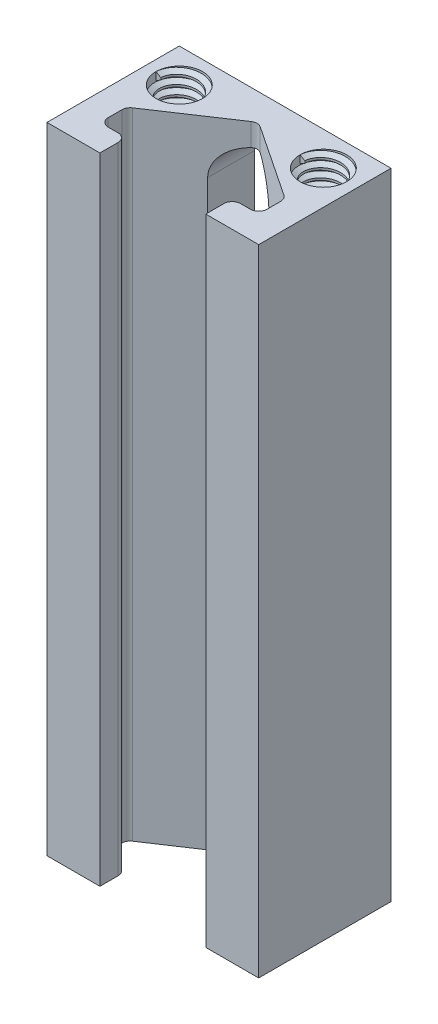
SolidWorks part; units mm, degrees
ref_plane "Front Plane" through (0, 0, 0) normal (0, 0, 1) x (1, 0, 0)
ref_plane "Top Plane" through (0, 0, 0) normal (0, 1, 0) x (1, 0, 0)
ref_plane "Right Plane" through (0, 0, 0) normal (1, 0, 0) x (0, 0, -1)
sketch "Sketch2" plane through (0, 0, 0) normal (0, 0, 1) x (1, 0, 0)
  line L0 (-71.4143, -70) -> (71.4143, -70)
  arc A0 (-71.4143, -70) -> (71.4143, -70) centre (0, 0) ccw
  point P5 (0, -70)
  point P6 (0, -100)
  dimension "D1" = 200
  dimension "D2" = 30
extrude "Boss-Extrude1" add sketch "Sketch2" along normal blind 127
sketch "Sketch3" plane through (0, 0, 0) normal (0, 1, 0) x (1, 0, 0)
  line L0 (-52.3643, -127) -> (-52.3643, -111.125)
  line L1 (71.4143, -127) -> (-71.4143, -127) construction
  line L2 (-52.3643, -111.125) -> (-26.9643, -111.125)
  line L3 (-26.9643, -111.125) -> (-26.9643, -127)
  line L4 (-26.9643, -127) -> (-33.3143, -127)
  line L5 (-33.3143, -127) -> (-33.3143, -123.825)
  line L6 (-33.3143, -123.825) -> (-30.1393, -123.825)
  line L7 (-30.1393, -123.825) -> (-30.1393, -120.65)
  line L8 (-30.1393, -120.65) -> (-39.6643, -114.3)
  line L9 (-39.6643, -114.3) -> (-49.1893, -120.65)
  line L10 (-49.1893, -120.65) -> (-49.1893, -123.825)
  line L11 (-49.1893, -123.825) -> (-46.0143, -123.825)
  line L12 (-46.0143, -123.825) -> (-46.0143, -127)
  line L13 (-46.0143, -127) -> (-52.3643, -127)
  line L14 (-71.4143, -127) -> (-71.4143, 0) construction
  point P1 (-52.3643, -111.125)
  point P5 (-26.9643, -111.125)
  point P6 (-27.4117, -111.125)
  point P16 (-51.891, -111.125)
  point P18 (-33.3143, -125.4125)
  dimension "D1" = 12.7
  dimension "D2" = 25.4
  dimension "D3" = 3.175
  dimension "D4" = 3.175
  dimension "D5" = 9.525
  dimension "D6" = 3.175
  dimension "D7" = 3.175
  dimension "D9" = 19.05
extrude "Boss-Extrude2" add sketch "Sketch3" along normal blind 76.2
fillet "Fillet1" radius 1 7 edges at (-46.0143, 38.1, 123.825) (-33.3143, 38.1, 123.825) (-30.1393, 38.1, 123.825) (-30.1393, 38.1, 120.65) (-39.6643, 38.1, 114.3) (-49.1893, 38.1, 120.65) (-49.1893, 38.1, 123.825)
sketch "Sketch5" plane through (0, 0, 111.125) normal (0, 0, -1) x (-1, 0, 0)
  line L0 (39.6643, 69.85) -> (39.6643, 6.35) construction
  line L1 (43.3393, 69.85) -> (43.3393, 6.35)
  line L2 (35.9893, 69.85) -> (35.9893, 6.35)
  line L3 (33.3143, 69.85) -> (46.0143, 69.85) construction
  line L6 (26.9643, 76.2) -> (52.3643, 76.2) construction
  line L7 (46.0143, 76.2) -> (46.0143, 0) construction
  line L8 (26.9643, 0) -> (52.3643, 0) construction
  line L9 (33.3143, 76.2) -> (33.3143, 0) construction
  arc A0 (43.3393, 69.85) -> (35.9893, 69.85) centre (39.6643, 69.85) ccw
  arc A1 (35.9893, 6.35) -> (43.3393, 6.35) centre (39.6643, 6.35) ccw
  point P2 (39.6643, 38.1)
  point P7 (46.0143, 31.75)
  point P12 (33.3143, 31.75)
  dimension "D1" = 7.35
  dimension "D2" = 6.35
  dimension "D3" = 6.35
extrude "Cut-Extrude1" cut sketch "Sketch5" against normal through all both and the other way through all
delete or keep bodies "Body-Delete/Keep 1" type delete bodies bodies 101
sketch "Sketch6" plane through (0, 76.2, 0) normal (0, 1, 0) x (1, 0, 0)
  line L0 (-48.3059, -115.1834) -> (-48.3059, -111.125) construction
  line L2 (-39.6643, -111.125) -> (-39.6643, -127) construction
  line L3 (-26.9643, -111.125) -> (-52.3643, -111.125) construction
  line L4 (-52.3643, -127) -> (-46.0143, -127) construction
  line L6 (-26.9643, -111.125) -> (-52.3643, -111.125) construction
  line L7 (-48.3059, -115.1834) -> (-52.3643, -115.1834) construction
  line L8 (-52.3643, -111.125) -> (-52.3643, -127) construction
  line L9 (-52.3643, -111.125) -> (-45.3793, -118.11) construction
  line L10 (-48.744, -120.3531) -> (-40.219, -114.6698) construction
  line L11 (-46.0546, -118.5602) -> (-46.7534, -117.5121) construction
  line L12 (-48.4587, -118.649) -> (-46.7534, -117.5121) construction
  line L13 (-51.1046, -115.1834) -> (-52.3643, -115.1834) construction
  circle A0 centre (-48.3059, -115.1834) radius 2.7987
  circle A3 centre (-31.0227, -115.1834) radius 2.7987
  dimension "D1" = 5.5974
extrude "Cut-Extrude2" cut sketch "Sketch6" against normal blind 25.4
thread "Thread1" pitch 1.0583 start angle 0, offset 0, length 0, pitch 1.0583, diameter 5.5974
ref_plane "Plane1" through (-51.1046, 76.2, 115.1834) normal (0, 0, 1) x (-1, 0, 0)
sketch "Thread Profile1" plane through (-51.1046, 76.2, 115.1834) normal (0, 0, 1) x (-1, 0, 0)
  line L0 (0, 0) -> (0, 1.0583) construction
  line L11 (0, 0) -> (0, 0.926)
  line L12 (0, 0.926) -> (-0.5728, 0.5953)
  line L13 (-0.5728, 0.5953) -> (-0.5728, 0.3307)
  line L15 (-0.5728, 0.3307) -> (0, 0)
  line L17 (-0.5728, 0.463) -> (0, 0.463) construction
  point P2 (0, 0)
  dimension "Pitch" = 1.0583
  dimension "Profile_Angle" = 60
  dimension "Profile_Land" = 0.2646
  dimension "Profile_Height" = 0.5728
thread "Thread2" pitch 1.0583 profile "Thread Profile2" start angle 0, offset 0, length 0, pitch 1.0583, diameter 5.5974
ref_plane "Plane2" through (-33.8214, 76.2, 115.1834) normal (0, 0, 1) x (-1, 0, 0)
sketch "Thread Profile2" plane through (-33.8214, 76.2, 115.1834) normal (0, 0, 1) x (-1, 0, 0)
  line L0 (0, 0) -> (0, 1.0583) construction
  line L11 (0, 0) -> (0, 0.926)
  line L12 (0, 0.926) -> (-0.5728, 0.5953)
  line L13 (-0.5728, 0.5953) -> (-0.5728, 0.3307)
  line L15 (-0.5728, 0.3307) -> (0, 0)
  line L17 (-0.5728, 0.463) -> (0, 0.463) construction
  point P2 (0, 0)
  dimension "Pitch" = 1.0583
  dimension "Profile_Angle" = 60
  dimension "Profile_Land" = 0.2646
  dimension "Profile_Height" = 0.5728
